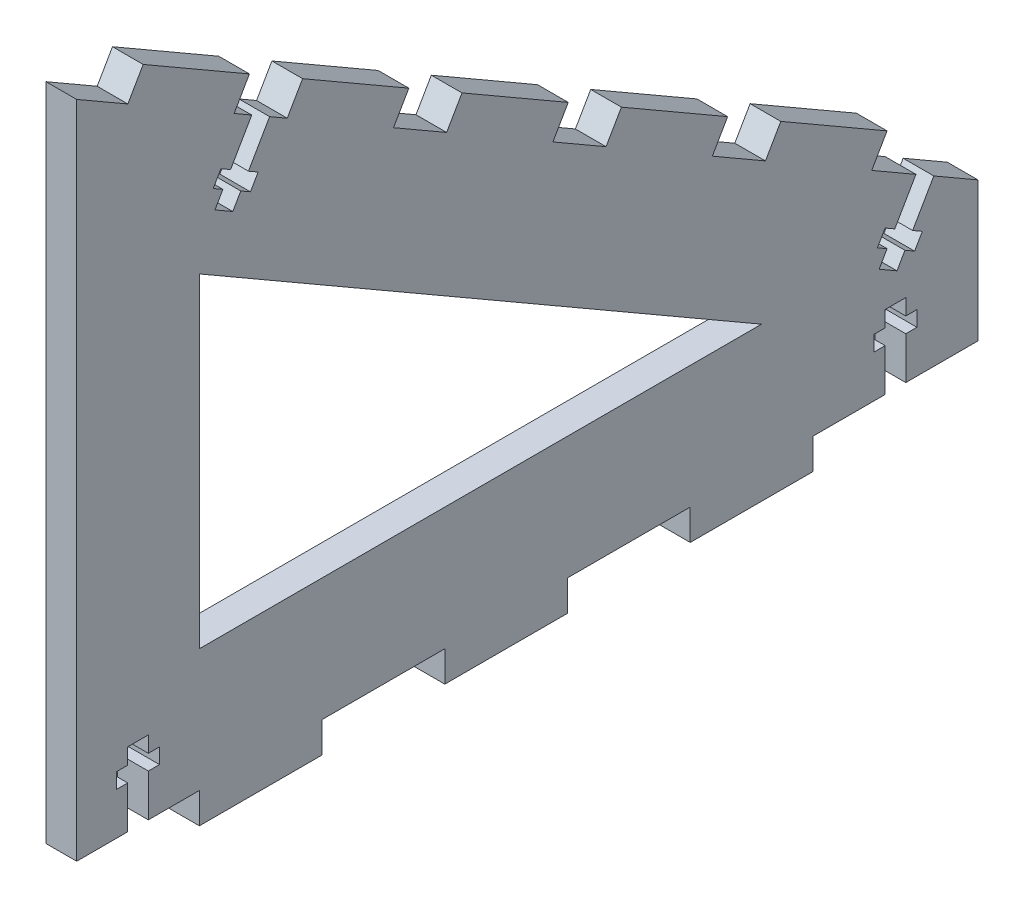
SolidWorks part; units mm, degrees
ref_plane "Front Plane" through (0, 0, 0) normal (0, 0, 1) x (1, 0, 0)
ref_plane "Top Plane" through (0, 0, 0) normal (0, 1, 0) x (1, 0, 0)
ref_plane "Right Plane" through (0, 0, 0) normal (1, 0, 0) x (0, 0, -1)
sketch "Sketch1" plane through (-32.0384, 0, 0) normal (-1, 0, 0) x (0, 0, 1)
  line L0 (-215.9, 95.25) -> (-215.9, 124.1125)
  line L1 (165.3114, 95.25) -> (152.9655, 95.25) construction
  line L2 (-215.9, 124.1125) -> (-29.3333, 231.8268)
  line L3 (-29.3333, 231.8268) -> (-29.3333, 95.25)
  line L4 (-29.3333, 95.25) -> (-215.9, 95.25)
  line L5 (-29.3333, 231.8268) -> (-42.2787, 224.3528) construction
  line L6 (-29.3333, 95.25) -> (-29.3333, 231.8268) construction
extrude "Boss-Extrude1" add sketch "Sketch1" along normal mid plane 6.35
sketch "Sketch2" plane through (-35.2134, 0, 0) normal (-1, 0, 0) x (0, 0, 1)
  line L14 (-54.7333, 120.65) -> (-54.7333, 187.8327)
  line L15 (-171.0972, 120.65) -> (-54.7333, 120.65)
  line L16 (-54.7333, 187.8327) -> (-171.0972, 120.65)
  line L17 (-54.7333, 120.65) -> (-54.7333, 187.8327)
  line L18 (-171.0972, 120.65) -> (-54.7333, 120.65)
  line L19 (-54.7333, 187.8327) -> (-171.0972, 120.65)
  dimension "D1" = 25.4
extrude "Cut-Extrude1" cut sketch "Sketch2" against normal blind 6.35
sketch "Sketch3" plane through (0, 186.5718, -107.7173) normal (0, 0.866, -0.5) x (1, 0, 0)
  line L0 (-35.2134, -90.51) -> (-35.2134, 124.9186) construction
  line L1 (-35.2134, 99.5186) -> (-28.8634, 99.5186)
  line L2 (-35.2134, 99.5186) -> (-35.2134, 74.1186)
  line L3 (-35.2134, 74.1186) -> (-28.8634, 74.1186)
  line L4 (-28.8634, 99.5186) -> (-28.8634, 74.1186)
  line L5 (-28.8634, -90.51) -> (-28.8634, 124.9186) construction
  dimension "D1" = 25.4
  dimension "D2" = 25.4
extrude "Boss-Extrude2" add sketch "Sketch3" along normal blind 6.35
pattern_linear "LPattern1" count 5 spacing 38.1 along (0, 0.5, 0.866) of "Boss-Extrude2"
sketch "Sketch4" plane through (0, 95.25, 0) normal (0, -1, 0) x (1, 0, 0)
  line L0 (-35.2134, -215.9) -> (-35.2134, -29.3333) construction
  line L1 (-35.2134, -54.7333) -> (-28.8634, -54.7333)
  line L2 (-35.2134, -54.7333) -> (-35.2134, -80.1333)
  line L3 (-35.2134, -80.1333) -> (-28.8634, -80.1333)
  line L4 (-28.8634, -54.7333) -> (-28.8634, -80.1333)
  line L5 (-28.8634, -215.9) -> (-28.8634, -29.3333) construction
  dimension "D1" = 25.4
  dimension "D2" = 25.4
extrude "Boss-Extrude3" add sketch "Sketch4" along normal blind 6.35
pattern_linear "LPattern2" count 3 spacing 50.8 along (0, 0, -1) of "Boss-Extrude3"
sketch "Sketch5" plane through (-28.8634, 0, 0) normal (1, 0, 0) x (0, 0, -1)
  line L0 (-152.9655, 95.25) -> (-165.3114, 95.25) construction
  line L1 (198.8167, 95.25) -> (198.8167, 119.6237) construction
  line L2 (215.9, 95.25) -> (181.7333, 95.25) construction
  line L3 (42.0333, 95.25) -> (42.0333, 127.2639) construction
  line L4 (54.7333, 95.25) -> (29.3333, 95.25) construction
  line L5 (-152.9655, 95.25) -> (-165.3114, 95.25) construction
  line B0 (196.6831, 95.25) -> (200.9503, 95.25)
  line B1 (200.9503, 107.188) -> (203.2617, 107.188)
  line B2 (203.2617, 107.188) -> (203.2617, 104.013)
  line B3 (203.2617, 104.013) -> (200.9503, 104.013)
  line B4 (200.9503, 104.013) -> (200.9503, 95.25)
  line B5 (200.9503, 107.188) -> (200.9503, 110.49)
  line B6 (200.9503, 110.49) -> (196.6831, 110.49)
  line B7 (196.6831, 107.188) -> (196.6831, 110.49)
  line B8 (196.6831, 104.013) -> (196.6831, 95.25)
  line B9 (194.3717, 104.013) -> (196.6831, 104.013)
  line B10 (194.3717, 107.188) -> (194.3717, 104.013)
  line B11 (196.6831, 107.188) -> (194.3717, 107.188)
  line B12 (39.8997, 95.25) -> (44.1669, 95.25)
  line B13 (44.1669, 107.188) -> (46.4783, 107.188)
  line B14 (46.4783, 107.188) -> (46.4783, 104.013)
  line B15 (46.4783, 104.013) -> (44.1669, 104.013)
  line B16 (44.1669, 104.013) -> (44.1669, 95.25)
  line B17 (44.1669, 107.188) -> (44.1669, 110.49)
  line B18 (44.1669, 110.49) -> (39.8997, 110.49)
  line B19 (39.8997, 107.188) -> (39.8997, 110.49)
  line B20 (39.8997, 104.013) -> (39.8997, 95.25)
  line B21 (37.5883, 104.013) -> (39.8997, 104.013)
  line B22 (37.5883, 107.188) -> (37.5883, 104.013)
  line B23 (39.8997, 107.188) -> (37.5883, 107.188)
sketch_block_instance "TSlot-1"
sketch_block "TSlot" parameters "D1"=3.302, "D2"=3.175
sketch_block_instance "TSlot-3"
extrude "Cut-Extrude2" cut sketch "Sketch5" against normal blind 6.35
sketch "Sketch6" plane through (-28.8634, 0, 0) normal (1, 0, 0) x (0, 0, -1)
  line L1 (51.3304, 219.1268) -> (73.3274, 206.4268) construction
  line L3 (183.3127, 142.9268) -> (205.3097, 130.2268) construction
  line L4 (204.9015, 130.4625) -> (196.0314, 115.099) construction
  line L5 (193.903, 136.8125) -> (215.9, 124.1125) construction
  line L6 (67.4199, 209.8375) -> (60.3001, 197.5056) construction
  line L7 (61.9207, 213.0125) -> (72.9192, 206.6625) construction
  line B0 (206.7492, 129.3957) -> (203.0537, 131.5293)
  line B1 (197.0847, 121.1907) -> (195.083, 122.3464)
  line B2 (195.083, 122.3464) -> (196.6705, 125.096)
  line B3 (196.6705, 125.096) -> (198.6722, 123.9403)
  line B4 (198.6722, 123.9403) -> (203.0537, 131.5293)
  line B5 (197.0847, 121.1907) -> (195.4337, 118.3311)
  line B6 (195.4337, 118.3311) -> (199.1292, 116.1975)
  line B7 (200.7802, 119.0571) -> (199.1292, 116.1975)
  line B8 (202.3677, 121.8067) -> (206.7492, 129.3957)
  line B9 (204.3695, 120.651) -> (202.3677, 121.8067)
  line B10 (202.782, 117.9014) -> (204.3695, 120.651)
  line B11 (200.7802, 119.0571) -> (202.782, 117.9014)
  line B12 (69.2677, 208.7707) -> (65.5722, 210.9043)
  line B13 (59.6032, 200.5657) -> (57.6015, 201.7214)
  line B14 (57.6015, 201.7214) -> (59.189, 204.471)
  line B15 (59.189, 204.471) -> (61.1907, 203.3153)
  line B16 (61.1907, 203.3153) -> (65.5722, 210.9043)
  line B17 (59.6032, 200.5657) -> (57.9522, 197.7061)
  line B18 (57.9522, 197.7061) -> (61.6477, 195.5725)
  line B19 (63.2987, 198.4321) -> (61.6477, 195.5725)
  line B20 (64.8862, 201.1817) -> (69.2677, 208.7707)
  line B21 (66.8879, 200.026) -> (64.8862, 201.1817)
  line B22 (65.3004, 197.2764) -> (66.8879, 200.026)
  line B23 (63.2987, 198.4321) -> (65.3004, 197.2764)
sketch_block_instance "TSlot-4"
sketch_block_instance "TSlot-5"
extrude "Cut-Extrude3" cut sketch "Sketch6" against normal blind 6.35
